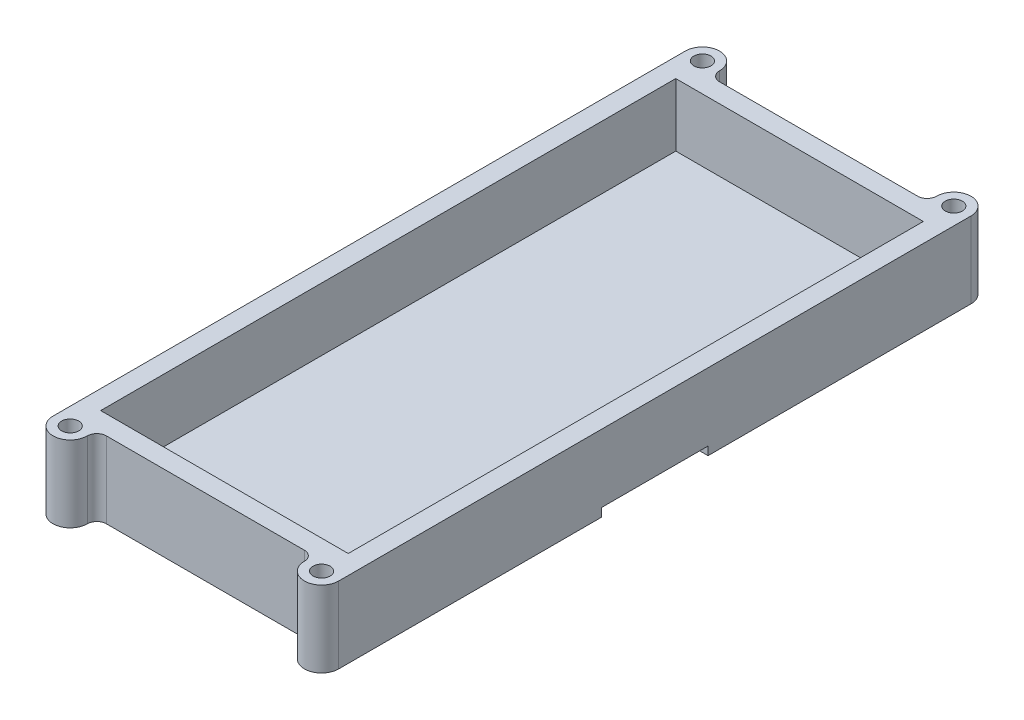
SolidWorks part; units mm, degrees
ref_plane "Front Plane" through (0, 0, 0) normal (0, 0, 1) x (1, 0, 0)
ref_plane "Top Plane" through (0, 0, 0) normal (0, 1, 0) x (1, 0, 0)
ref_plane "Right Plane" through (0, 0, 0) normal (1, 0, 0) x (0, 0, -1)
sketch "Sketch1" plane through (0, 0, 0) normal (0, 1, 0) x (1, 0, 0)
  line L1 (32.5, -75.5) -> (-32.5, -75.5)
  line L2 (32.5, -75.5) -> (32.5, 75.5)
  line L3 (32.5, 75.5) -> (-32.5, 75.5)
  line L4 (-32.5, -75.5) -> (-32.5, 75.5)
  line L9 (-37.5, 75.5) -> (-37.5, -75.5)
  line L10 (0, 7.9485) -> (0, -7.5303) construction
  line L11 (-10.0763, 0) -> (10.4307, 0) construction
  line L13 (37.5, 75.5) -> (37.5, -75.5)
  line L14 (-37.5, -75.5) -> (-37.5, -83)
  line L15 (-28.5, -83) -> (-28.5, -80.5)
  line L16 (-28.5, -80.5) -> (28.5, -80.5)
  line L17 (28.5, -83) -> (28.5, -80.5)
  line L18 (37.5, -75.5) -> (37.5, -83)
  line L19 (28.5, 83) -> (28.5, 80.5)
  line L20 (37.5, 75.5) -> (37.5, 83)
  line L21 (-28.5, 83) -> (-28.5, 80.5)
  line L22 (-37.5, 75.5) -> (-37.5, 83)
  line L23 (-28.5, 80.5) -> (28.5, 80.5)
  arc A0 (-37.5, -83) -> (-28.5, -83) centre (-33, -83) ccw
  circle A1 centre (-33, -83) radius 2.25
  circle A2 centre (33, -83) radius 2.25
  arc A3 (37.5, -83) -> (28.5, -83) centre (33, -83) cw
  circle A4 centre (33, 83) radius 2.25
  arc A5 (37.5, 83) -> (28.5, 83) centre (33, 83) ccw
  circle A6 centre (-33, 83) radius 2.25
  arc A7 (-37.5, 83) -> (-28.5, 83) centre (-33, 83) cw
  point P5 (0, -75.5)
  point P7 (32.5, 0)
  dimension "D5" = 4.5
  dimension "D6" = 4.5
  dimension "D3" = 5
  dimension "D7" = 2.5
  dimension "D1" = 65
  dimension "D2" = 151
  dimension "D4" = 5
extrude "Boss-Extrude1" add sketch "Sketch1" along normal blind 20
sketch "Sketch3" plane through (0, 0, 0) normal (0, -1, 0) x (1, 0, 0)
  line L8 (32.5, -75.5) -> (-32.5, -75.5) construction
  line L9 (-32.5, 75.5) -> (32.5, 75.5)
  line L10 (-32.5, 75.5) -> (-32.5, -75.5)
  line L11 (-32.5, -75.5) -> (32.5, -75.5)
  line L12 (32.5, 75.5) -> (32.5, -75.5)
  line L13 (-32.5, -75.5) -> (-32.5, 75.5) construction
  line L14 (32.5, 75.5) -> (32.5, -75.5) construction
extrude "Boss-Extrude2" add sketch "Sketch3" against normal blind 3.5
sketch "Sketch4" plane through (-37.5, 0, 0) normal (-1, 0, 0) x (0, 0, 1)
  line L0 (-83, 0) -> (83, 0) construction
  line L1 (-13.97, 2.2) -> (13.97, 2.2)
  line L2 (-13.97, 2.2) -> (-13.97, 0)
  line L3 (-13.97, 0) -> (13.97, 0)
  line L4 (13.97, 2.2) -> (13.97, 0)
  point P6 (0, 0)
  point P7 (0, 0)
  dimension "D1" = 27.94
  dimension "D2" = 2.2
extrude "Cut-Extrude1" cut sketch "Sketch4" against normal through all
fillet "Fillet1" radius 2.5 4 edges at (28.5, 10, 80.5) (-28.5, 10, 80.5) (28.5, 10, -80.5) (-28.5, 10, -80.5)
